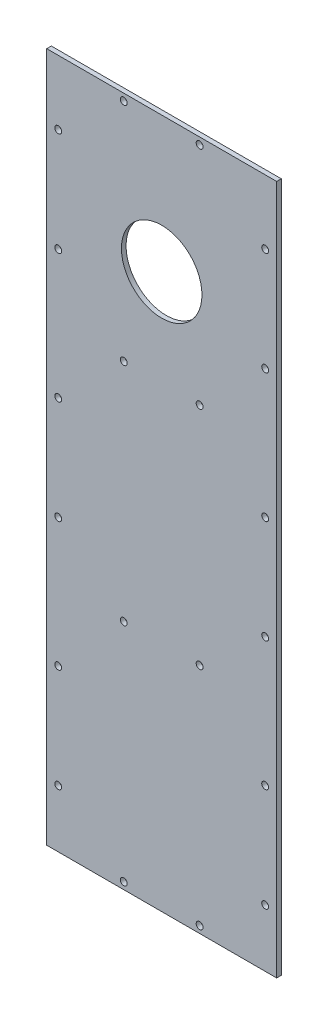
SolidWorks part; units mm, degrees
material "Alumina"
ref_plane "Front Plane" through (0, 0, 0) normal (0, 0, 1) x (1, 0, 0)
ref_plane "Top Plane" through (0, 0, 0) normal (0, 1, 0) x (1, 0, 0)
ref_plane "Right Plane" through (0, 0, 0) normal (1, 0, 0) x (0, 0, -1)
sketch "Sketch1" plane through (0, 0, 0) normal (0, 0, 1) x (1, 0, 0)
  line L1 (50, -150) -> (-50, -150)
  line L2 (50, -150) -> (50, 150)
  line L3 (50, 150) -> (-50, 150)
  line L4 (-50, -150) -> (-50, 150)
  line L5 (50, -150) -> (-50, 150) construction
  line L6 (50, 150) -> (-50, -150) construction
  point P0 (0, 0)
  dimension "D1" = 100
  dimension "D2" = 300
extrude "Boss-Extrude1" add sketch "Sketch1" along normal blind 2
sketch "Sketch2" plane through (0, 0, 2) normal (0, 0, 1) x (1, 0, 0)
  line L0 (-50, 150) -> (-50, -150) construction
  line L1 (50, 150) -> (-50, 150) construction
  line L2 (-50, -150) -> (50, -150) construction
  line L4 (0, -1.1) -> (0, 1.1) construction
  line L5 (-45, 122) -> (-45, 21) construction
  circle A0 centre (-45, 122) radius 1.5
  circle A1 centre (-45, 77) radius 1.5
  circle A2 centre (45, 122) radius 1.5
  circle A3 centre (45, 77) radius 1.5
  circle A4 centre (-45, 21) radius 1.5
  circle A5 centre (-45, -24) radius 1.5
  circle A6 centre (45, 21) radius 1.5
  circle A7 centre (45, -24) radius 1.5
  circle A8 centre (-45, -80) radius 1.5
  circle A9 centre (-45, -125) radius 1.5
  circle A10 centre (45, -80) radius 1.5
  circle A11 centre (45, -125) radius 1.5
  circle A13 centre (16.5, -147) radius 1.5
  circle A14 centre (-16.5, -147) radius 1.5
  circle A15 centre (-16.5, -49) radius 1.5
  circle A16 centre (16.5, -49) radius 1.5
  circle A17 centre (-16.5, 49) radius 1.5
  circle A18 centre (16.5, 49) radius 1.5
  circle A19 centre (-16.5, 147) radius 1.5
  circle A20 centre (16.5, 147) radius 1.5
  dimension "D1" = 3
  dimension "D3" = 28
  dimension "D4" = 3
  dimension "D6" = 5
  dimension "D10" = 3
  dimension "D11" = 33
  dimension "D13" = 3
  dimension "D14" = 90
  dimension "D15" = 5
  dimension "D16" = 3
  dimension "D2" = 5
  dimension "D9" = 25
  dimension "D17" = 101
  dimension "D7" = 2
  dimension "D8" = 3
  dimension "D12" = 4
extrude "Cut-Extrude1" cut sketch "Sketch2" against normal blind 10
sketch "Sketch3" plane through (0, 0, 0) normal (0, 0, -1) x (-1, 0, 0)
  line L0 (-50, 150) -> (50, 150) construction
  line L1 (-50, -150) -> (-50, 150) construction
  circle A0 centre (0, 91) radius 17.5
  dimension "D2" = 35
  dimension "D3" = 50
  dimension "D1" = 59
extrude "Cut-Extrude2" cut sketch "Sketch3" against normal blind 10
